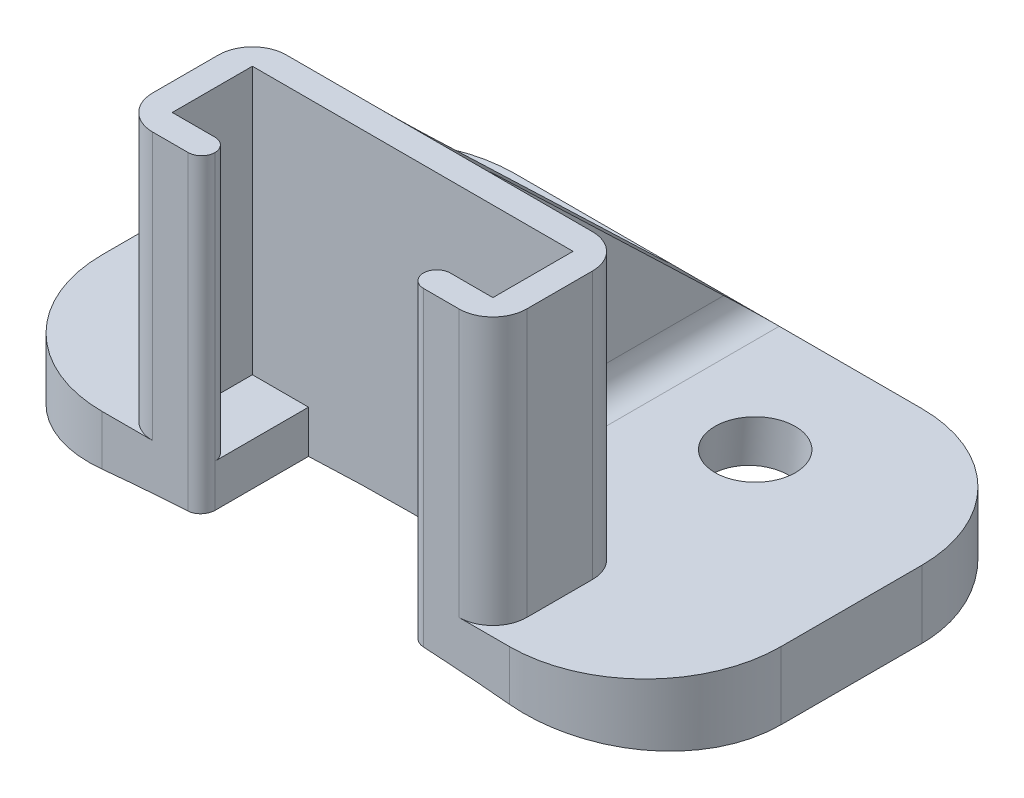
SolidWorks part; units mm, degrees
ref_plane "Front Plane" through (0, 0, 0) normal (0, 0, 1) x (1, 0, 0)
ref_plane "Top Plane" through (0, 0, 0) normal (0, 1, 0) x (1, 0, 0)
ref_plane "Right Plane" through (0, 0, 0) normal (1, 0, 0) x (0, 0, -1)
sketch "Sketch1" plane through (0, 0, 0) normal (0, 1, 0) x (1, 0, 0)
  line L0 (6, -10.985) -> (7, -10.985)
  line L1 (-12.7, 4.445) -> (12.7, 4.445)
  line L2 (-12.7, 4.445) -> (-12.7, -19.3675)
  line L3 (-12.7, -19.3675) -> (12.7, -19.3675)
  line L4 (12.7, 4.445) -> (12.7, -19.3675)
  line L5 (-6, -6.985) -> (6, -6.985)
  line L6 (-6, -6.985) -> (-6, -13.985)
  line L7 (-6, -13.985) -> (6, -13.985)
  line L8 (6, -6.985) -> (6, -13.985)
  line L9 (7, -10.985) -> (7, -5.985)
  line L10 (7, -5.985) -> (-7, -5.985)
  line L11 (-7, -5.985) -> (-7, -10.985)
  line L12 (-7, -10.985) -> (-6, -10.985)
  line L13 (6, -10.985) -> (3.9, -10.985)
  line L14 (3.9, -10.985) -> (3.9, -9.985)
  line L15 (3.9, -9.985) -> (6, -9.985)
  line L16 (-6, -10.985) -> (-3.9, -10.985)
  line L17 (-3.9, -10.985) -> (-3.9, -9.985)
  line L18 (-3.9, -9.985) -> (-6, -9.985)
  line L19 (-3.9, -9.985) -> (-3.9, -6.985)
  line L20 (3.9, -9.985) -> (3.9, -6.985)
  line L21 (0, -7.3881) -> (0, 0) construction
  line L22 (-3, -13.985) -> (-3, -17.16)
  line L23 (-3, -17.16) -> (3, -17.16)
  line L24 (3, -17.16) -> (3, -13.985)
  point P23 (0, -19.3675)
  point P24 (0, -17.16)
  point P27 (0, -6.985)
  dimension "D1" = 12
  dimension "D2" = 7
  dimension "D3" = 1
  dimension "D4" = 1
  dimension "D5" = 7.8
  dimension "D6" = 3
  dimension "D7" = 1
  dimension "D8" = 6.985
  dimension "D9" = 23.8125
  dimension "D10" = 25.4
  dimension "D11" = 4.445
  dimension "D12" = 3.175
  dimension "D13" = 6
sketch "Sketch2" plane through (0, 0, 0) normal (0, 0, 1) x (1, 0, 0)
  line L0 (0, 0) -> (0, -76.859) construction
  circle A0 centre (0, -76.859) radius 78.359
  dimension "D1" = 156.718
  dimension "D2" = 76.859
ref_axis "Axis1" through (0, -76.859, 0) along (0, 0, 1)
ref_plane "Plane1" through (-5.5819, -76.4515, 0) normal (0.0728, 0.9973, 0) x (0, 0, 1)
sketch "Sketch3" plane through (-5.5819, -76.4515, 0) normal (0.0728, 0.9973, 0) x (0, 0, 1)
  line L0 (0, -72.7623) -> (0, 83.9557) construction
  circle A0 centre (0, 5.5967) radius 1.5
  dimension "D1" = 3
extrude "Boss-Extrude1" add sketch "Sketch1" along normal blind 3 contours L3 L21 L7 L6 L12 L11 L10 L1 L2 | L21 L3 L4 L1 L10 L9 L0 L8 L7 | L5 L21 L10 L11 L12 L6 | L21 L5 L8 L0 L9 L10 | L20 L15 L8 L5 | L18 L19 L5 L6 | L15 L14 L13 L8 | L17 L18 L6 L16 region at (6.086, 0, 10.485) region at (4.95, 0, 10.485) region at (4.95, 0, 8.485) region at (-0.086, 0, 6.485) region at (-4.95, 0, 8.485) region at (-4.95, 0, 10.485) region at (0, 0, -4.0968)
extrude "Cut-Extrude1" cut sketch "Sketch3" along normal through all contours A0
mirror "Mirror1" about plane through (0, 0, 0) normal (1, 0, 0) of "Cut-Extrude1"
extrude "Boss-Extrude2" add sketch "Sketch1<8>" along normal blind 10 from surface contours L5 L21 L10 L11 L12 L6 | L17 L18 L6 L16 | L15 L14 L13 L8 | L21 L5 L8 L0 L9 L10 region at (6.086, 0, 10.485) region at (4.95, 0, 10.485) region at (-0.086, 0, 6.485) region at (-4.95, 0, 10.485) starting at face at (-4.3267, 3, 0)
sketch "Sketch1<8>" plane through (0, 0, 0) normal (0, 1, 0) x (1, 0, 0) same geometry as "Sketch1"
extrude "Cut-Extrude2" cut sketch "Sketch2" against normal through all both and the other way through all
sketch "Sketch4" plane through (0, 0, 19.3675) normal (0, 0, 1) x (1, 0, 0)
  line L1 (-12.7, 3) -> (12.7, 3)
  line L2 (-12.7, 3) -> (-12.7, 0.464)
  line L3 (-12.7, 0.464) -> (12.7, 0.464)
  line L4 (12.7, 3) -> (12.7, 0.464)
extrude "Cut-Extrude3" cut sketch "Sketch4" against normal up to surface (8.3825 mm away) up to face at (-5.6334, 5.78, 10.985)
sketch "Sketch6" plane through (0, 0, 0) normal (1, 0, 0) x (0, 0, -1)
  line L0 (-5.985, 13) -> (4.445, 3)
  line L1 (4.445, 3) -> (-5.985, 3)
  line L2 (-5.985, 3) -> (-5.985, 13)
extrude "Boss-Extrude3" add sketch "Sketch6" along normal mid plane 2.54
fillet "Fillet1" radius 5.08 4 edges at (-12.7, 1.732, 10.985) (-12.7, 1.732, -4.445) (12.7, 1.732, -4.445) (12.7, 1.732, 10.985)
fillet "Fillet2" radius 1.27 4 edges at (-7, 8, 5.985) (7, 8, 5.985) (7, 8, 10.985) (-7, 8, 10.985)
fillet "Fillet3" radius 0.508 4 edges at (3.9, 7.2014, 10.985) (-3.9, 7.2014, 10.985) (3.9, 8, 9.985) (-3.9, 8, 9.985)
fillet "Fillet4" radius 1.016 4 edges at (1.27, 3, 0.77) (-1.27, 3, 0.77) (-1.27, 8, 5.985) (1.27, 8, 5.985)
equation "\"D2@Sketch2\"=(6.17/2)*1in - 1.5mm"
equation "\"D1@Sketch3\"=3mm"
